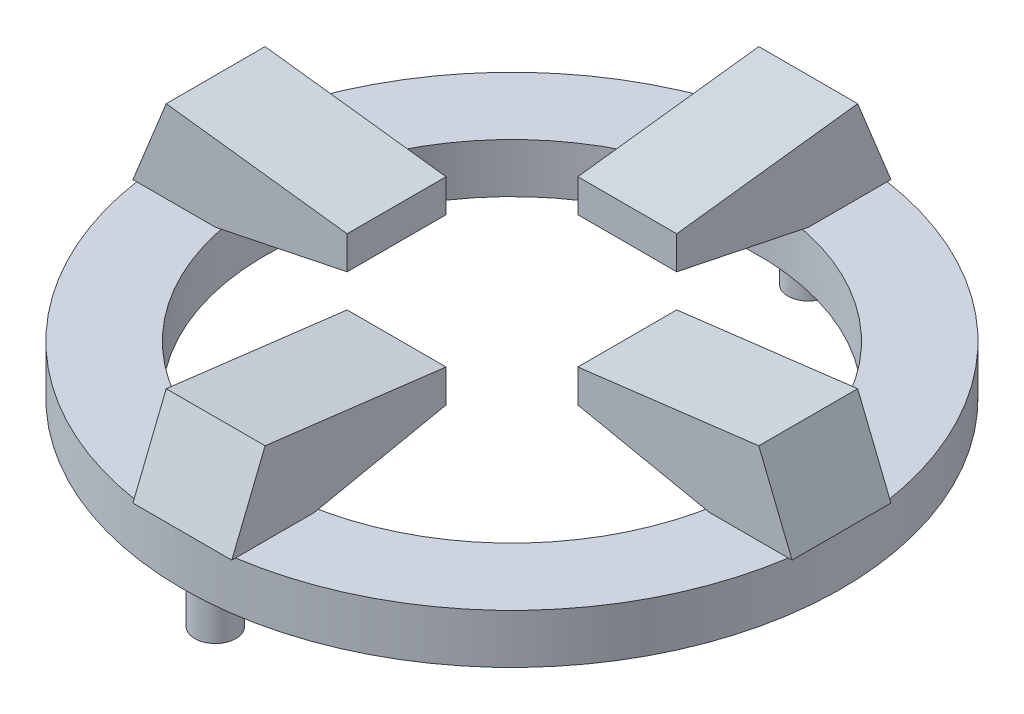
SolidWorks part; units mm, degrees
material "Cast Stainless Steel"
ref_plane "Front Plane" through (0, 0, 0) normal (0, 0, 1) x (1, 0, 0)
ref_plane "Top Plane" through (0, 0, 0) normal (0, 1, 0) x (1, 0, 0)
ref_plane "Right Plane" through (0, 0, 0) normal (1, 0, 0) x (0, 0, -1)
sketch "Sketch1" plane through (0, 0, 0) normal (0, 1, 0) x (1, 0, 0)
  circle A0 centre (0, 0) radius 15
  circle A1 centre (0, 0) radius 20
  dimension "D1" = 40
  dimension "D2" = 30
extrude "Boss-Extrude1" add sketch "Sketch1" along normal blind 3
sketch "Sketch2" plane through (0, 0, 0) normal (1, 0, 0) x (0, 0, -1)
  line L0 (20, 3) -> (17.9799, 8)
  line L1 (17.9799, 8) -> (7, 6.6518)
  line L2 (7, 6.6518) -> (7, 4.6518)
  line L3 (7, 4.6518) -> (15, 3)
  line L4 (20, 3) -> (-20, 3) construction
  line L5 (0, 8.6597) -> (0, -6.2509) construction
  line L6 (15, 3) -> (20, 3)
  line L7 (-7, 4.6518) -> (-15, 3)
  line L8 (-7, 6.6518) -> (-7, 4.6518)
  line L9 (-17.9799, 8) -> (-7, 6.6518)
  line L10 (-20, 3) -> (-17.9799, 8)
  line L11 (-15, 3) -> (-20, 3)
  dimension "D1" = 5
  dimension "D2" = 8
  dimension "D3" = 2
  dimension "D4" = 68
  dimension "D5" = 105
extrude "Boss-Extrude2" add sketch "Sketch2" along normal blind 3 and the other way blind 3
sketch "Sketch3" plane through (0, 0, 0) normal (0, 0, 1) x (1, 0, 0)
  line L0 (20, 3) -> (17.9799, 8)
  line L1 (17.9799, 8) -> (7, 6.6518)
  line L2 (7, 6.6518) -> (7, 4.6518)
  line L3 (7, 4.6518) -> (15, 3)
  line L4 (15, 3) -> (20, 3)
  line L5 (0, 10.8313) -> (0, -6.5097) construction
  line L6 (-7, 4.6518) -> (-15, 3)
  line L7 (-7, 6.6518) -> (-7, 4.6518)
  line L8 (-17.9799, 8) -> (-7, 6.6518)
  line L9 (-20, 3) -> (-17.9799, 8)
  line L10 (-15, 3) -> (-20, 3)
  dimension "D1" = 5
  dimension "D2" = 8
  dimension "D3" = 2
  dimension "D4" = 68
  dimension "D5" = 105
extrude "Boss-Extrude3" add sketch "Sketch3" along normal blind 3 and the other way blind 3
sketch "Sketch4" plane through (0, 0, 0) normal (0, -1, 0) x (1, 0, 0)
  circle A1 centre (0, 18) radius 1.25
  circle A2 centre (0, -18) radius 1.25
  circle A3 centre (0, 0) radius 20 construction
  dimension "D1" = 18
  dimension "D2" = 2.5
  dimension "D3" = 18
extrude "Boss-Extrude4" add sketch "Sketch4" along normal blind 3
